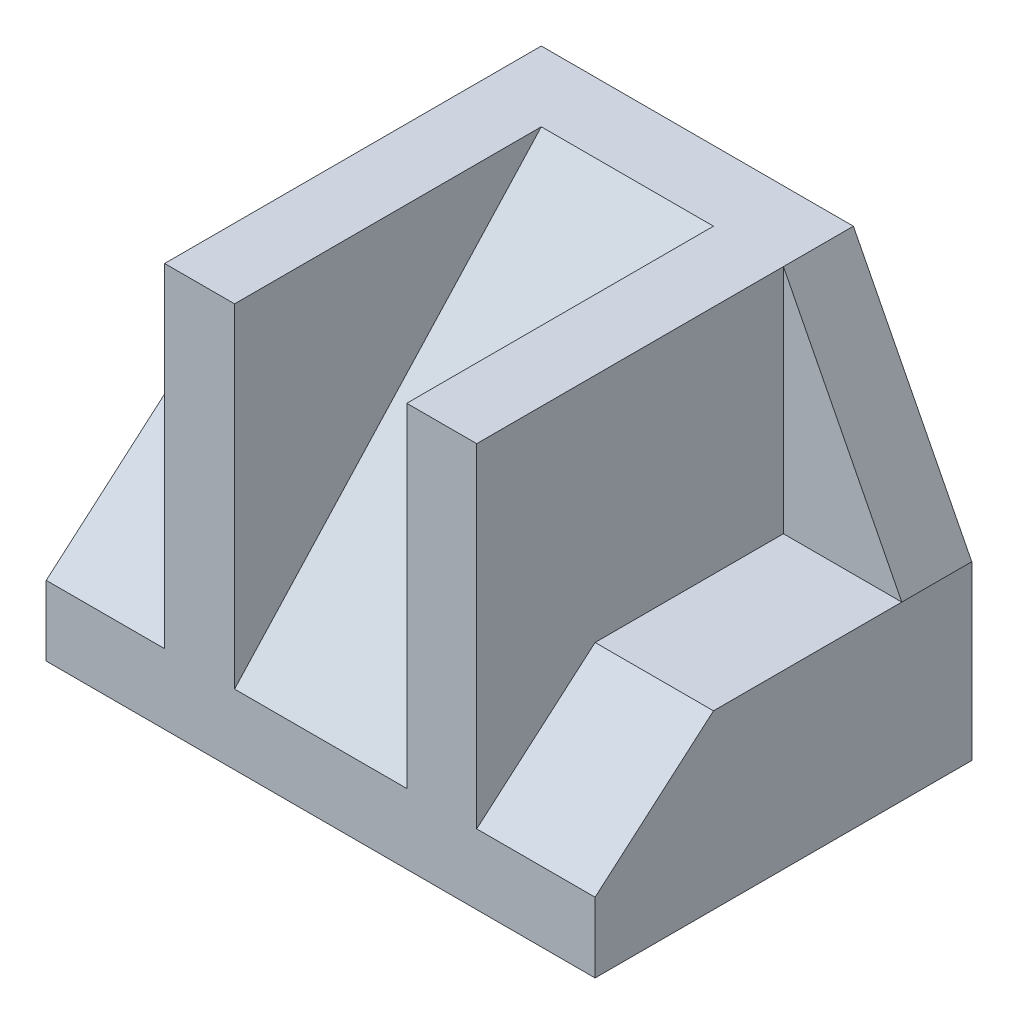
SolidWorks part; units mm, degrees
ref_plane "Front Plane" through (0, 0, 0) normal (0, 0, 1) x (1, 0, 0)
ref_plane "Top Plane" through (0, 0, 0) normal (0, 1, 0) x (1, 0, 0)
ref_plane "Right Plane" through (0, 0, 0) normal (1, 0, 0) x (0, 0, -1)
sketch "Sketch1" plane through (0, 0, 0) normal (1, 0, 0) x (0, 0, -1)
  line L0 (57, 75) -> (57, 32)
  line L1 (0, 0) -> (70, 0)
  line L2 (0, 0) -> (0, 75)
  line L3 (0, 75) -> (70, 75)
  line L4 (70, 0) -> (70, 75)
  line L5 (57, 32) -> (22, 32)
  line L6 (22, 32) -> (0, 13)
  line L7 (0, 13) -> (57, 75)
  dimension "D1" = 13
  dimension "D2" = 32
  dimension "D3" = 22
  dimension "D4" = 70
  dimension "D5" = 75
  dimension "D6" = 13
extrude "Boss-Extrude1" add sketch "Sketch1" along normal mid plane 102 contours L5 L6 L2 L1 L4 L3 L0 region at (0, 23.3136, -43.3837)
extrude "Boss-Extrude2" add sketch "Sketch1<3>" along normal blind 13 from offset 16 contours L7 L6 L5 L0 | L2 L7 L3 region at (0, 54.3333, -19) region at (0, 45.3369, -42.344)
sketch "Sketch1<3>" plane through (0, 0, 0) normal (1, 0, 0) x (0, 0, -1) same geometry as "Sketch1"
sketch "Sketch2" plane through (0, 0, -57) normal (0, 0, 1) x (1, 0, 0)
  line L0 (29, 75) -> (51, 32)
  line L1 (51, 32) -> (51, 75)
  line L2 (51, 75) -> (29, 75)
extrude "Cut-Extrude1" cut sketch "Sketch2" against normal up to next
mirror "Mirror1" about plane through (0, 0, 0) normal (1, 0, 0) of "Cut-Extrude1", "Boss-Extrude2"
extrude "Boss-Extrude3" add sketch "Sketch1<4>" along normal up to vertex (16 mm away) and the other way up to vertex (16 mm away) contours L7 L6 L5 L0 region at (0, 45.3369, -42.344) up to point (16, 75, -57) other way up to point (-16, 75, -57)
sketch "Sketch1<4>" plane through (0, 0, 0) normal (1, 0, 0) x (0, 0, -1) same geometry as "Sketch1"
